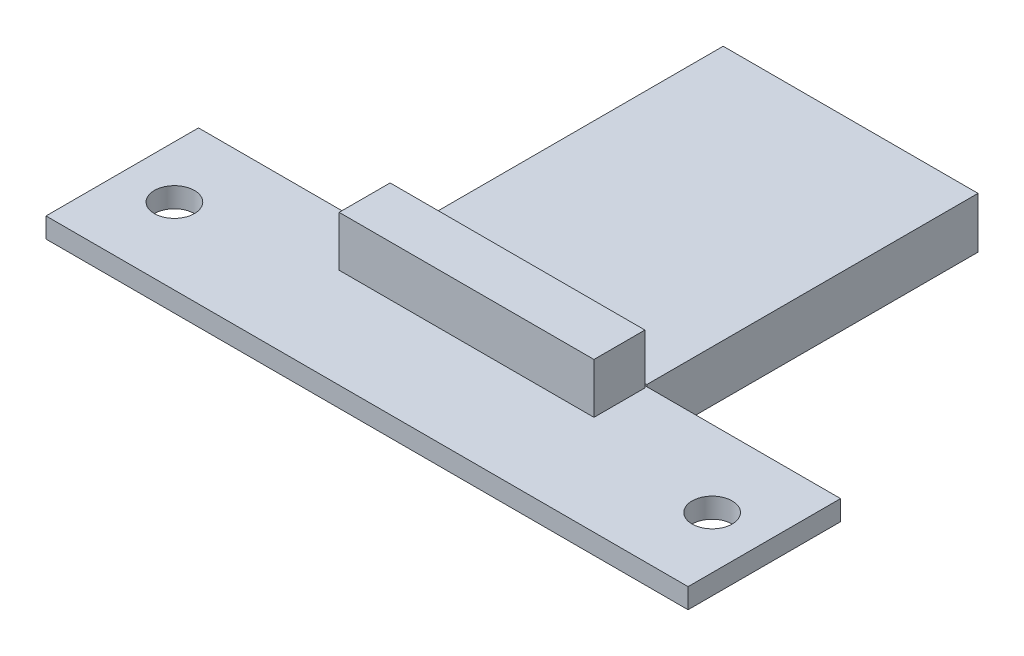
SolidWorks part; units mm, degrees
ref_plane "Спереди" through (0, 0, 0) normal (0, 0, 1) x (1, 0, 0)
ref_plane "Сверху" through (0, 0, 0) normal (0, 1, 0) x (1, 0, 0)
ref_plane "Справа" through (0, 0, 0) normal (1, 0, 0) x (0, 0, -1)
sketch "Sketch1" plane through (0, 0, 0) normal (0, 1, 0) x (1, 0, 0)
  line L1 (-16, 3.8) -> (16, 3.8)
  line L2 (-16, 3.8) -> (-16, -3.8)
  line L3 (-16, -3.8) -> (16, -3.8)
  line L4 (16, 3.8) -> (16, -3.8)
  line L5 (-16, 3.8) -> (16, -3.8) construction
  line L6 (-16, -3.8) -> (16, 3.8) construction
  point P0 (0, 0)
  dimension "D1" = 32
  dimension "D2" = 7.6
extrude "Boss-Extrude1" add sketch "Sketch1" along normal blind 1
sketch "Sketch2" plane through (0, 1, 0) normal (0, 1, 0) x (1, 0, 0)
  line L0 (-13.4, 0) -> (13.4, 0) construction
  circle A0 centre (-13.4, 0) radius 1
  circle A1 centre (13.4, 0) radius 1
  point P4 (0, 0)
  dimension "D1" = 2
  dimension "D2" = 26.8
extrude "Cut-Extrude1" cut sketch "Sketch2" against normal through all
sketch "Sketch3" plane through (0, 0, 0) normal (0, -1, 0) x (1, 0, 0)
  line L0 (-9.5, 0) -> (9.5, 0) construction
  line L1 (0, 1.1) -> (0, 0) construction
  line L2 (-10.3, 1.1) -> (-8.7, 1.1)
  line L3 (-10.3, 1.1) -> (-10.3, -1.1)
  line L4 (-10.3, -1.1) -> (-8.7, -1.1)
  line L5 (-8.7, 1.1) -> (-8.7, -1.1)
  line L6 (-10.3, 1.1) -> (-8.7, -1.1) construction
  line L7 (-10.3, -1.1) -> (-8.7, 1.1) construction
  line L8 (8.7, 1.1) -> (10.3, 1.1)
  line L9 (8.7, 1.1) -> (8.7, -1.1)
  line L10 (8.7, -1.1) -> (10.3, -1.1)
  line L11 (10.3, 1.1) -> (10.3, -1.1)
  line L12 (8.7, 1.1) -> (10.3, -1.1) construction
  line L13 (8.7, -1.1) -> (10.3, 1.1) construction
  line L14 (-0.8, 2.2) -> (0.8, 2.2)
  line L15 (-0.8, 2.2) -> (-0.8, 0)
  line L16 (-0.8, 0) -> (0.8, 0)
  line L17 (0.8, 2.2) -> (0.8, 0)
  line L18 (-0.8, 2.2) -> (0.8, 0) construction
  line L19 (-0.8, 0) -> (0.8, 2.2) construction
  point P3 (0, 1.1)
  point P4 (0, 0)
  dimension "D1" = 1.6
  dimension "D2" = 2.2
  dimension "D3" = 9.5
extrude "Boss-Extrude2" add sketch "Sketch3" along normal blind 1
sketch "Sketch4" plane through (0, 0, -3.8) normal (0, 0, -1) x (-1, 0, 0)
  line L0 (0, -0.17) -> (0, 0) construction
  line L1 (-6.35, 1.1) -> (6.35, 1.1)
  line L2 (-6.35, 1.1) -> (-6.35, -1.44)
  line L3 (-6.35, -1.44) -> (6.35, -1.44)
  line L4 (6.35, 1.1) -> (6.35, -1.44)
  line L5 (-6.35, 1.1) -> (6.35, -1.44) construction
  line L6 (-6.35, -1.44) -> (6.35, 1.1) construction
  line L8 (-16, 1) -> (16, 1) construction
  point P0 (0, -0.17)
  dimension "D1" = 2.54
  dimension "D2" = 12.7
  dimension "D3" = 0.1
extrude "Boss-Extrude3" add sketch "Sketch4" along normal blind 16.5
sketch "Sketch5" plane through (0, 1, 0) normal (0, 1, 0) x (1, 0, 0)
  line L0 (-6.35, 20.3) -> (-6.35, 3.8) construction
  line L1 (-6.35, 1.16) -> (6.35, 1.16)
  line L2 (-6.35, 1.16) -> (-6.35, 3.7)
  line L3 (-6.35, 3.7) -> (6.35, 3.7)
  line L4 (6.35, 1.16) -> (6.35, 3.7)
  line L5 (-6.35, 1.16) -> (6.35, 3.7) construction
  line L6 (-6.35, 3.7) -> (6.35, 1.16) construction
  line L7 (6.35, 20.3) -> (6.35, 3.8) construction
  line L8 (-6.35, 3.8) -> (-16, 3.8) construction
  point P0 (0, 2.43)
  dimension "D1" = 2.54
  dimension "D2" = 0.1
extrude "Boss-Extrude4" add sketch "Sketch5" along normal blind 2.5
